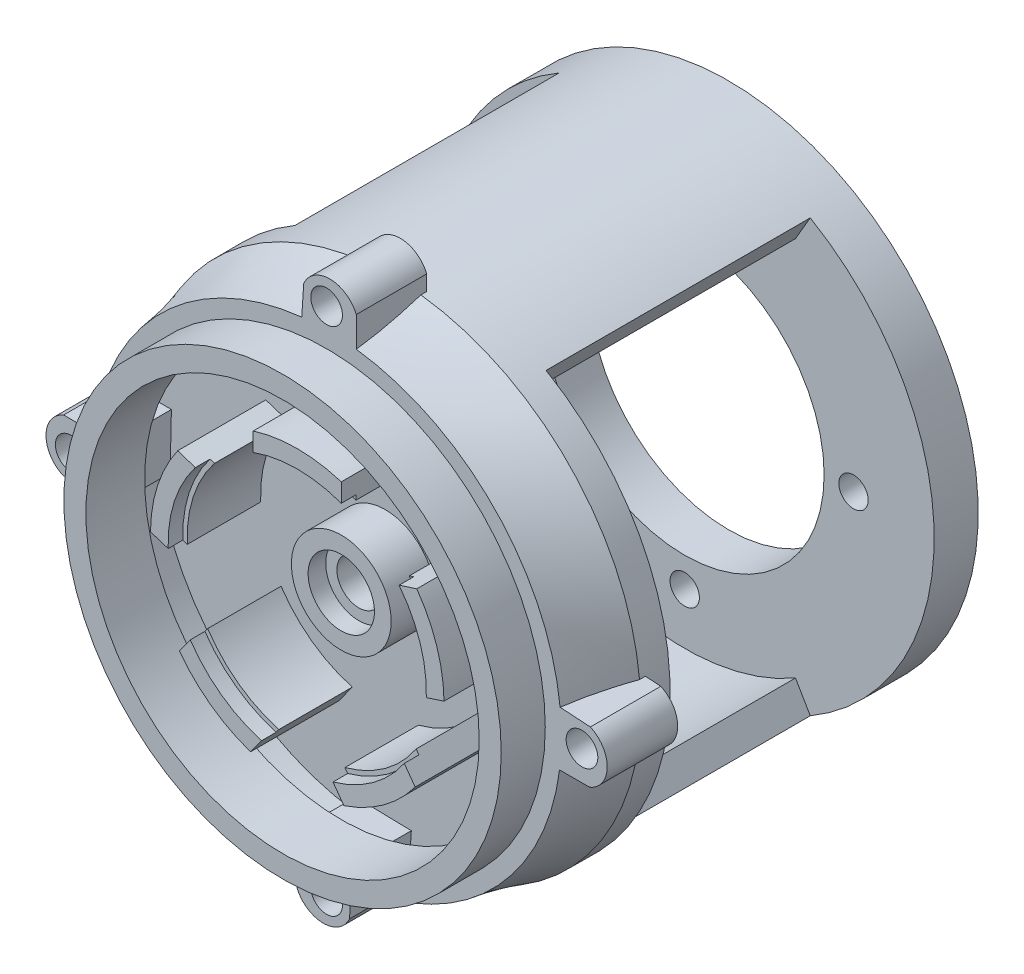
SolidWorks part; units mm, degrees
ref_plane "Ön Düzlem" through (0, 0, 0) normal (0, 0, 1) x (1, 0, 0)
ref_plane "Üst Düzlem" through (0, 0, 0) normal (0, 1, 0) x (1, 0, 0)
ref_plane "Sağ Düzlem" through (0, 0, 0) normal (1, 0, 0) x (0, 0, -1)
sketch "Sketch1" plane through (0, 0, 0) normal (0, 0, 1) x (1, 0, 0)
  circle A0 centre (0, 0) radius 85
extrude "Boss-Extrude1" add sketch "Sketch1" along normal blind 10
ref_plane "Plane1" through (0, 0, 32) normal (0, 0, 1) x (1, 0, 0)
sketch "Sketch2" plane through (0, 0, 32) normal (0, 0, 1) x (1, 0, 0)
  circle A0 centre (0, 0) radius 80
sketch "Sketch3" plane through (0, 0, 10) normal (0, 0, 1) x (1, 0, 0)
  circle A0 centre (0, 0) radius 85 construction
  circle A1 centre (0, 0) radius 85
loft "Loft1" add profiles "Sketch3", "Sketch2" connector at (-84.9859, -1.5487, 10) connector at (-77.5611, -19.6029, 32)
sketch "Sketch4" plane through (0, 0, 32) normal (0, 0, 1) x (1, 0, 0)
  circle A0 centre (0, 0) radius 74.5
extrude "Boss-Extrude2" add sketch "Sketch4" along normal blind 15
sketch "Sketch5" plane through (0, 0, 47) normal (0, 0, 1) x (1, 0, 0)
  circle A0 centre (0, 0) radius 67
extrude "Cut-Extrude1" cut sketch "Sketch5" against normal blind 20
sketch "Sketch6" plane through (0, 0, 27) normal (0, 0, 1) x (1, 0, 0)
  circle A0 centre (0, 0) radius 78
extrude "Cut-Extrude2" cut sketch "Sketch6" against normal blind 15
sketch "Sketch7" plane through (0, 0, 32) normal (0, 0, 1) x (1, 0, 0)
  line L0 (0, 0) -> (0, 73.0113) construction
  line L4 (10.112, 72.8689) -> (10.112, 89.5979)
  line L5 (-8.8607, 73.2984) -> (-7.7976, 89.8544)
  line L6 (-8.8607, 73.2984) -> (10.112, 72.8689)
  arc A4 (10.112, 89.5979) -> (-7.7976, 89.8544) centre (1.1015, 85.8364) ccw
  point P10 (6.4612, 85.5926)
  point P14 (-6.4612, 85.5926)
extrude "Boss-Extrude3" add sketch "Sketch7" against normal blind 24
pattern_circular "CirPattern1" count 4 over 360 about axis through (0, 0, 47) along (0, 0, 1) of "Boss-Extrude3"
sketch "Sketch10" plane through (0, 0, 32) normal (0, 0, 1) x (1, 0, 0)
  line L0 (0, 0) -> (0, 87) construction
sketch "Sketch12" plane through (0, 0, 32) normal (0, 0, 1) x (1, 0, 0)
  circle A0 centre (0, 87) radius 5
hole_wizard "M12x1.25 Tapped Hole1" positions "3DSketch1" profile "Sketch13" tap size "M12x1.25" standard "Ansi Metric"
sketch3d "3DSketch1"
  point P0 (0, 87, 32)
sketch "Sketch13" plane through (0, 87, 32) normal (1, 0, 0) x (0, -1, 0)
  line L0 (0, 0) -> (0, 23.4946)
  line L1 (0, 23.4946) -> (5.4, 20.25)
  line L2 (5.4, 20.25) -> (5.4, 0)
  line L5 (5.4, 0) -> (0, 0)
  line L10 (0, 23.4946) -> (-5.4, 20.25) construction
  line L11 (0, -6.35) -> (0, 107.95) construction
  dimension "Tap Drill Dia." = 10.8
  dimension "Tap Drill Depth" = 20.25
  dimension "Drill Angle" = 118
cosmetic thread "Hole Thread1" parameters "D1"=20.25, "D2"=12
pattern_circular "CirPattern2" count 4 over 360 about axis through (0, 0, 47) along (0, 0, 1) of "M12x1.25 Tapped Hole1"
sketch "Sketch14" plane through (0, 0, 12) normal (0, 0, 1) x (1, 0, 0)
  circle A0 centre (0, 0) radius 17
extrude "Boss-Extrude4" add sketch "Sketch14" along normal blind 15
sketch "Sketch15" plane through (0, 0, 27) normal (0, 0, 1) x (1, 0, 0)
  circle A0 centre (0, 0) radius 11.3
extrude "Cut-Extrude3" cut sketch "Sketch15" against normal blind 6
sketch "Sketch16" plane through (0, 0, 21) normal (0, 0, 1) x (1, 0, 0)
  circle A0 centre (0, 0) radius 7.5
extrude "Cut-Extrude4" cut sketch "Sketch16" against normal through all
sketch "Sketch17" plane through (0, 0, 12) normal (0, 0, 1) x (1, 0, 0)
  line L0 (33.1834, 26.5539) -> (40.7272, 29.005)
  line L1 (15, 39.7649) -> (15, 47.697)
  line L2 (-15, 39.7649) -> (-15, 47.697)
  line L3 (42.454, -1.9778) -> (49.9978, 0.4733)
  line L4 (35.5085, -23.3537) -> (40.1708, -29.7709)
  line L5 (11.238, -40.9873) -> (15.9003, -47.4044)
  line L6 (-11.238, -40.9873) -> (-15.9003, -47.4044)
  line L7 (-35.5085, -23.3537) -> (-40.1708, -29.7709)
  line L8 (-42.454, -1.9778) -> (-49.9978, 0.4733)
  line L9 (-33.1834, 26.5539) -> (-40.7272, 29.005)
  arc A0 (15, 39.7649) -> (-15, 39.7649) centre (0, 0) ccw
  arc A1 (15, 47.697) -> (-15, 47.697) centre (0, 0) ccw
  arc A2 (42.454, -1.9778) -> (33.1834, 26.5539) centre (0, 0) ccw
  arc A3 (49.9978, 0.4733) -> (40.7272, 29.005) centre (0, 0) ccw
  arc A4 (11.238, -40.9873) -> (35.5085, -23.3537) centre (0, 0) ccw
  arc A5 (15.9003, -47.4044) -> (40.1708, -29.7709) centre (0, 0) ccw
  arc A6 (-35.5085, -23.3537) -> (-11.238, -40.9873) centre (0, 0) ccw
  arc A7 (-40.1708, -29.7709) -> (-15.9003, -47.4044) centre (0, 0) ccw
  arc A8 (-33.1834, 26.5539) -> (-42.454, -1.9778) centre (0, 0) ccw
  arc A9 (-40.7272, 29.005) -> (-49.9978, 0.4733) centre (0, 0) ccw
  dimension "D1" = 5
extrude "Boss-Extrude5" add sketch "Sketch17" along normal blind 30
sketch "Sketch18" plane through (0, 0, 0) normal (0, 0, -1) x (-1, 0, 0)
  line L0 (37.7399, 64.8128) -> (42.7719, 73.4545)
  line L1 (37.7399, -64.8128) -> (42.7719, -73.4545)
  line L2 (-37.7399, 64.8128) -> (-42.7719, 73.4545)
  line L3 (-37.7399, -64.8128) -> (-42.7719, -73.4545)
  circle A0 centre (0, 0) radius 85 construction
  arc A1 (42.7719, 73.4545) -> (-42.7719, 73.4545) centre (0, 0) ccw
  arc A2 (37.7399, 64.8128) -> (-37.7399, 64.8128) centre (0, 0) ccw
  circle A3 centre (0, 0) radius 75 construction
  circle A4 centre (0, 0) radius 85 construction
  arc A5 (-37.7399, -64.8128) -> (37.7399, -64.8128) centre (0, 0) ccw
  arc A6 (-42.7719, -73.4545) -> (42.7719, -73.4545) centre (0, 0) ccw
  dimension "D1" = 10
  dimension "D2" = 2
extrude "Boss-Extrude6" add sketch "Sketch18" along normal blind 90
sketch "Sketch19" plane through (0, 0, -90) normal (0, 0, -1) x (-1, 0, 0)
  circle A0 centre (0, 0) radius 85
extrude "Boss-Extrude7" add sketch "Sketch19" along normal blind 15
sketch "Sketch20" plane through (0, 0, -105) normal (0, 0, -1) x (-1, 0, 0)
  circle A0 centre (0, 0) radius 47.5
extrude "Cut-Extrude5" cut sketch "Sketch20" against normal blind 15
sketch "Sketch21" plane through (0, 0, -105) normal (0, 0, -1) x (-1, 0, 0)
  line L2 (0, 0) -> (0, 87) construction
  circle A1 centre (0, 57.5) radius 5
extrude "Cut-Extrude6" cut sketch "Sketch21" against normal blind 15
pattern_circular "CirPattern3" count 4 over 360 about axis through (0, 0, -105) along (0, 0, -1) of "Cut-Extrude6"
sketch "Sketch22" plane through (0, 0, 0) normal (0, 0, -1) x (-1, 0, 0)
  circle A0 centre (0, 0) radius 16.5
extrude "Cut-Extrude7" cut sketch "Sketch22" against normal blind 9
fillet "Fillet1" radius 5 1 edges at (-16.5, 0, 9)
sketch "Sketch23" plane through (0, 0, 42) normal (0, 0, 1) x (1, 0, 0)
  circle A0 centre (0, 0) radius 44
extrude "Cut-Extrude8" cut sketch "Sketch23" against normal blind 5
